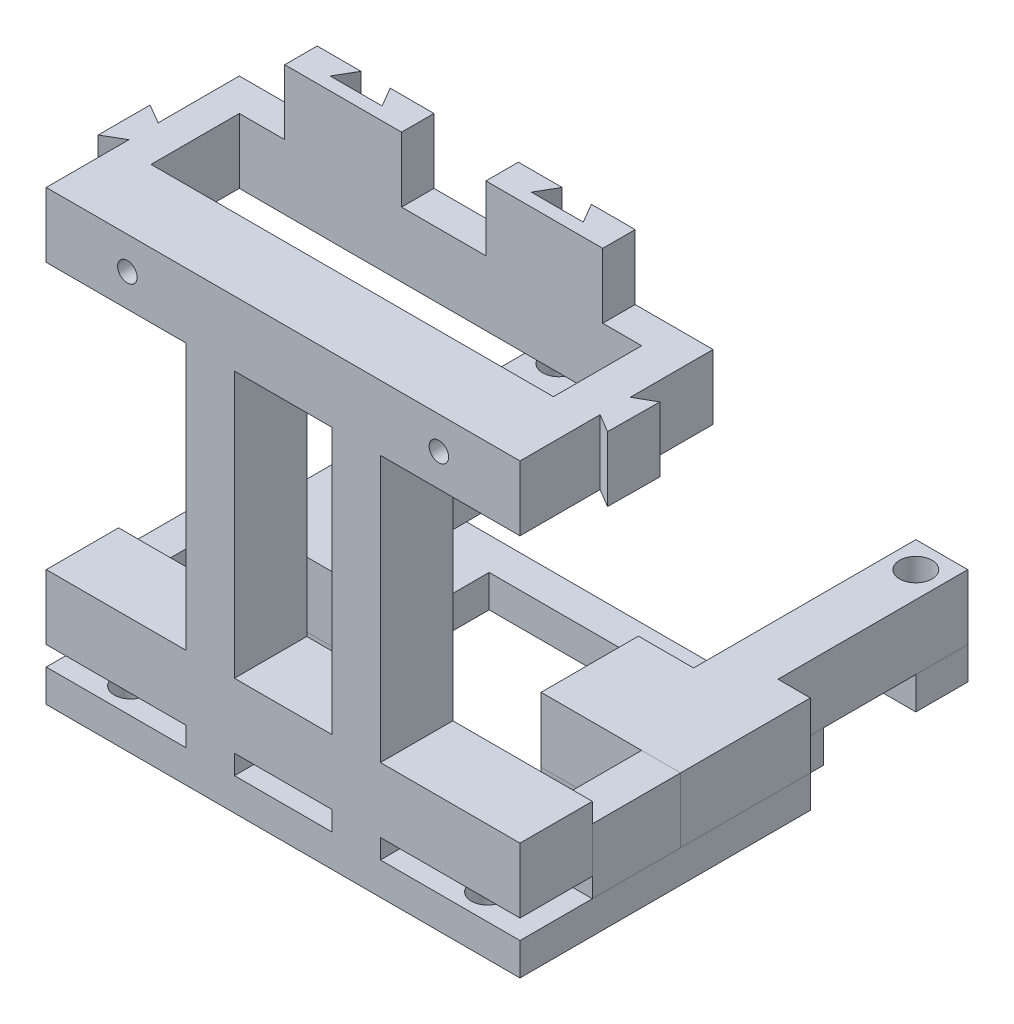
SolidWorks part; units mm, degrees
ref_plane "Front" through (0, 0, 0) normal (0, 0, 1) x (1, 0, 0)
ref_plane "Top" through (0, 0, 0) normal (0, 1, 0) x (1, 0, 0)
ref_plane "Right" through (0, 0, 0) normal (1, 0, 0) x (0, 0, -1)
sketch "Эскиз1" plane through (0, 0, 0) normal (0, 1, 0) x (1, 0, 0)
  line L0 (0, 17.2297) -> (0, -30.0047) construction
  line L1 (-31.5, 1.575) -> (31.5, 1.575)
  line L2 (-31.5, 1.575) -> (-31.5, -1.575)
  line L3 (-31.5, -1.575) -> (31.5, -1.575)
  line L4 (31.5, 1.575) -> (31.5, -1.575)
  line L5 (-31.5, 1.575) -> (31.5, -1.575) construction
  line L6 (-31.5, -1.575) -> (31.5, 1.575) construction
  line L7 (-23.5, -9.575) -> (23.5, -9.575)
  line L8 (-31.5, -1.575) -> (-23.5, -1.575)
  line L9 (-31.5, -1.575) -> (-31.5, -9.575)
  line L10 (-31.5, -9.575) -> (-23.5, -9.575)
  line L11 (-23.5, -1.575) -> (-23.5, -9.575)
  line L12 (-31.5, -1.575) -> (-23.5, -9.575) construction
  line L13 (-31.5, -9.575) -> (-23.5, -1.575) construction
  line L14 (23.5, -1.575) -> (31.5, -1.575)
  line L15 (23.5, -1.575) -> (23.5, -9.575)
  line L16 (23.5, -9.575) -> (31.5, -9.575)
  line L17 (31.5, -1.575) -> (31.5, -9.575)
  line L18 (23.5, -1.575) -> (31.5, -9.575) construction
  line L19 (23.5, -9.575) -> (31.5, -1.575) construction
  line L21 (-31.5, -9.575) -> (-36.5, -9.575)
  line L22 (-31.5, -9.575) -> (-31.5, 15.175)
  line L23 (-31.5, 15.175) -> (-36.5, 15.175)
  line L24 (-36.5, -9.575) -> (-36.5, 15.175)
  line L25 (31.5, -9.575) -> (36.5, -9.575)
  line L26 (31.5, -9.575) -> (31.5, 15.175)
  line L27 (31.5, 15.175) -> (36.5, 15.175)
  line L28 (36.5, -9.575) -> (36.5, 15.175)
  line L29 (-36.5, 15.175) -> (-15, 15.175)
  line L30 (-36.5, 15.175) -> (-36.5, 35.175)
  line L31 (-36.5, 35.175) -> (-15, 35.175)
  line L32 (-15, 15.175) -> (-15, 35.175)
  line L33 (36.5, 15.175) -> (15, 15.175)
  line L34 (36.5, 15.175) -> (36.5, 35.175)
  line L35 (36.5, 35.175) -> (15, 35.175)
  line L36 (15, 15.175) -> (15, 35.175)
  line L37 (-31.5, 64.425) -> (-23.5, 64.425)
  line L38 (-31.5, 64.425) -> (-31.5, 56.425)
  line L39 (-31.5, 56.425) -> (-23.5, 56.425)
  line L40 (-23.5, 64.425) -> (-23.5, 56.425)
  line L41 (-31.5, 64.425) -> (-23.5, 56.425) construction
  line L42 (-31.5, 56.425) -> (-23.5, 64.425) construction
  line L43 (23.5, 64.425) -> (31.5, 64.425)
  line L44 (23.5, 64.425) -> (23.5, 56.425)
  line L45 (23.5, 56.425) -> (31.5, 56.425)
  line L46 (31.5, 64.425) -> (31.5, 56.425)
  line L47 (23.5, 64.425) -> (31.5, 56.425) construction
  line L48 (23.5, 56.425) -> (31.5, 64.425) construction
  line L49 (-15, 35.175) -> (-31.5, 35.175)
  line L50 (-15, 35.175) -> (-15, 42.175)
  line L51 (-15, 42.175) -> (-31.5, 42.175)
  line L52 (-31.5, 35.175) -> (-31.5, 42.175)
  line L53 (15, 35.175) -> (31.5, 35.175)
  line L54 (15, 35.175) -> (15, 42.175)
  line L55 (15, 42.175) -> (31.5, 42.175)
  line L56 (31.5, 35.175) -> (31.5, 42.175)
  line L57 (-15, 42.175) -> (15, 42.175)
  line L58 (-15, 42.175) -> (-15, 37.175)
  line L59 (-15, 37.175) -> (15, 37.175)
  line L60 (15, 42.175) -> (15, 37.175)
  circle A0 centre (-27.5, -5.575) radius 2.5
  circle A1 centre (27.5, -5.575) radius 2.5
  circle A2 centre (-27.5, 60.425) radius 2.5
  circle A3 centre (27.5, 60.425) radius 2.5
  point P0 (0, 0)
  dimension "D1" = 5
  dimension "D2" = 55
  dimension "D10" = 5
  dimension "D12" = 25.25
  dimension "D3" = 8
  dimension "D4" = 3.15
  dimension "D5" = 8
  dimension "D6" = 5
  dimension "D7" = 16.75
  dimension "D8" = 21.5
  dimension "D9" = 20
  dimension "D11" = 8
  dimension "D13" = 7
  dimension "D14" = 5
extrude "Бобышка-Вытянуть1" add sketch "Эскиз1" along normal blind 5 contours L4 L1 L2 L3 | L11 L3 L9 L10 A0 | L17 L3 L15 L16 A1 | L15 L3 L11 L7 | L24 L21 L9 L2 L22 L23 | L29 L32 L31 L30 L23 | L36 L33 L27 L34 L35 | L25 L28 L27 L26 L4 L17 | L40 L37 L38 L39 A2 | L46 L43 L44 L45 A3 | L52 L31 L50 L51 | L35 L56 L55 L54 | L50 L59 L54 L57 region at (0, 0, 0) region at (-34, 0, -2.8) region at (34, 0, -2.8) region at (-27.5, 0, 1.6881) region at (-25.75, 0, -25.175) region at (31.3869, 0, 5.575) region at (25.75, 0, -25.175) region at (0, 0, 5.575) region at (-23.25, 0, -38.675) region at (23.25, 0, -38.675) region at (0, 0, -39.675) region at (-27.5, 0, -64.3119) region at (27.5, 0, -64.3119)
sketch "Эскиз2" plane through (0, 5, 0) normal (0, 1, 0) x (1, 0, 0)
  line L0 (-31.5, 1.575) -> (31.5, 1.575) construction
  line L1 (-15, 1.575) -> (-7.5, 1.575)
  line L2 (-15, 1.575) -> (-15, -9.575)
  line L3 (-15, -9.575) -> (-7.5, -9.575)
  line L4 (-7.5, 1.575) -> (-7.5, -9.575)
  line L5 (-36.5, -9.575) -> (36.5, -9.575) construction
  line L6 (0, 1.575) -> (0, -9.575) construction
  line L7 (7.5, 1.575) -> (15, 1.575)
  line L8 (7.5, 1.575) -> (7.5, -9.575)
  line L9 (7.5, -9.575) -> (15, -9.575)
  line L10 (15, 1.575) -> (15, -9.575)
  dimension "D1" = 7.5
  dimension "D2" = 7.5
extrude "Бобышка-Вытянуть2" add sketch "Эскиз2" along normal blind 64
sketch "Эскиз3" plane through (0, 0, 9.575) normal (0, 0, 1) x (1, 0, 0)
  line L0 (7.5, 69) -> (15, 69) construction
  line L1 (36.5, 69) -> (-36.5, 69)
  line L2 (36.5, 69) -> (36.5, 59)
  line L3 (36.5, 59) -> (-36.5, 59)
  line L4 (-36.5, 69) -> (-36.5, 59)
  line L6 (0, 0) -> (0, 5) construction
  line L7 (-36.5, 0) -> (36.5, 0) construction
  line L8 (-7.5, 5) -> (7.5, 5) construction
  line L9 (-36.5, 5) -> (-36.5, 0) construction
  line L11 (-36.5, 18) -> (36.5, 18)
  line L12 (-36.5, 18) -> (-36.5, 8)
  line L13 (-36.5, 8) -> (36.5, 8)
  line L14 (36.5, 18) -> (36.5, 8)
  circle A0 centre (-24, 64) radius 1.5
  circle A1 centre (24, 64) radius 1.5
  dimension "D2" = 48
  dimension "D4" = 3
  dimension "D1" = 10
  dimension "D3" = 5
extrude "Бобышка-Вытянуть3" add sketch "Эскиз3" against normal up to surface (11.15 mm away) up to face at (-2, 30.8333, -1.575)
sketch "Эскиз4" plane through (0, 5, 0) normal (0, 1, 0) x (1, 0, 0)
  line L0 (-31.5, 15.175) -> (-15, 15.175) construction
  line L1 (-31.5, 64.425) -> (-23.5, 64.425)
  line L2 (-31.5, 64.425) -> (-31.5, 15.175)
  line L3 (-31.5, 15.175) -> (-23.5, 15.175)
  line L4 (-23.5, 64.425) -> (-23.5, 15.175)
  line L5 (-36.5, -9.575) -> (-36.5, 35.175) construction
  line L6 (-31.5, 15.175) -> (-36.5, 15.175)
  line L7 (-31.5, 15.175) -> (-31.5, 23.175)
  line L8 (-31.5, 23.175) -> (-36.5, 23.175)
  line L9 (-36.5, 15.175) -> (-36.5, 23.175)
  line L10 (-15, 15.175) -> (-15, 37.175) construction
  line L11 (-23.5, 15.175) -> (-15, 15.175)
  line L12 (-23.5, 15.175) -> (-23.5, 30.175)
  line L13 (-23.5, 30.175) -> (-15, 30.175)
  line L14 (-15, 15.175) -> (-15, 30.175)
  line L15 (0, 42.175) -> (0, 37.175) construction
  line L16 (31.5, 42.175) -> (-31.5, 42.175) construction
  line L17 (-15, 37.175) -> (15, 37.175) construction
  line L18 (36.5, -9.575) -> (36.5, 35.175) construction
  line L19 (36.5, 15.175) -> (36.5, 35.175)
  line L20 (23.5, 64.425) -> (23.5, 15.175)
  line L21 (23.5, 15.175) -> (36.5, 15.175)
  line L22 (36.5, 35.175) -> (31.5, 35.175)
  line L23 (31.5, 15.175) -> (15, 15.175) construction
  line L24 (15, 15.175) -> (15, 37.175) construction
  line L25 (23.5, 15.175) -> (15, 15.175)
  line L26 (23.5, 15.175) -> (23.5, 30.175)
  line L27 (23.5, 30.175) -> (15, 30.175)
  line L28 (15, 15.175) -> (15, 30.175)
  line L29 (31.5, 35.175) -> (31.5, 64.425)
  line L30 (31.5, 64.425) -> (23.5, 64.425)
  circle A0 centre (-27.5, 60.425) radius 2.5
  circle A1 centre (-27.5, 60.425) radius 2.5 construction
  circle A2 centre (27.5, 60.425) radius 2.5
  circle A3 centre (27.5, 60.425) radius 2.5 construction
  line M8 (36.5, -9.575) -> (36.5, 35.175)
  line M9 (36.5, 35.175) -> (31.5, 35.175)
  line M10 (31.5, 35.175) -> (31.5, 42.175)
  line M11 (31.5, 42.175) -> (-31.5, 42.175)
  line M12 (-31.5, 42.175) -> (-31.5, 35.175)
  line M14 (-36.5, 35.175) -> (-36.5, -9.575)
  line M19 (-31.5, 15.175) -> (-15, 15.175)
  line M20 (-15, 15.175) -> (-15, 37.175)
  line M22 (15, 37.175) -> (15, 15.175)
  line M23 (15, 15.175) -> (31.5, 15.175)
  dimension "D1" = 8
  dimension "D2" = 15
  dimension "D3" = 15
extrude "Бобышка-Вытянуть4" add sketch "Эскиз4" along normal blind 10 separate body contours L4 L2 M11 M12 M19 | L4 L1 L2 A0 M11 | L13 L4 M19 M20 | L21 L20 M23 M8 M9 M10 M11 | L20 L27 M22 M23 | L29 L30 L20 A2 M11 | L2 L8 L6 M14 region at (27.5, 5, -52.4166) region at (29.557, 5, -27.5674) region at (-27.5, 5, -52.4166) region at (-27.5, 5, -28.675) region at (-19.25, 5, -22.675) region at (-34, 5, -19.175) region at (19.25, 5, -22.675)
sketch "Эскиз5" plane through (0, 0, -1.575) normal (0, 0, -1) x (-1, 0, 0)
  line L0 (-30.5, 5) -> (-30.5, 87) construction
  line L1 (-36.5, 5) -> (-30.5, 5)
  line L2 (-36.5, 5) -> (-36.5, 15)
  line L3 (-36.5, 15) -> (-30.5, 15)
  line L4 (-30.5, 5) -> (-30.5, 15)
  line L5 (31.5, 5) -> (31.5, 87) construction
  line L6 (36.5, 5) -> (31.5, 5)
  line L7 (36.5, 5) -> (36.5, 15)
  line L8 (36.5, 15) -> (31.5, 15)
  line L9 (31.5, 5) -> (31.5, 15)
  line L10 (-36.5, 8) -> (-36.5, 18) construction
  line L11 (36.5, 18) -> (36.5, 8) construction
extrude "Бобышка-Вытянуть7" add sketch "Эскиз5" along normal up to surface (13.6 mm away) separate body up to face at (25.75, 10, -15.175)
sketch "Эскиз6" plane through (0, 0, -1.575) normal (0, 0, -1) x (-1, 0, 0)
  line L0 (-30.5, 5) -> (-30.5, 87) construction
  line L1 (-36.5, 69) -> (-30.5, 69)
  line L2 (-36.5, 69) -> (-36.5, 59)
  line L3 (-36.5, 59) -> (-30.5, 59)
  line L4 (-30.5, 69) -> (-30.5, 59)
  line L5 (-15, 59) -> (-36.5, 59) construction
  line L6 (31.5, 5) -> (31.5, 87) construction
  line L7 (36.5, 69) -> (31.5, 69)
  line L8 (36.5, 69) -> (36.5, 59)
  line L9 (36.5, 59) -> (31.5, 59)
  line L10 (31.5, 69) -> (31.5, 59)
  line L11 (36.5, 59) -> (15, 59) construction
extrude "Бобышка-Вытянуть8" add sketch "Эскиз6" along normal up to surface (13.6 mm away) separate body up to face at (25.75, 10, -15.175)
sketch "Эскиз7" plane through (0, 0, -15.175) normal (0, 0, -1) x (-1, 0, 0)
  line L1 (-36.5, 69) -> (36.5, 69)
  line L2 (-36.5, 69) -> (-36.5, 59)
  line L3 (-36.5, 59) -> (36.5, 59)
  line L4 (36.5, 69) -> (36.5, 59)
extrude "Бобышка-Вытянуть9" add sketch "Эскиз7" along normal blind 5
sketch "Эскиз9" plane through (0, 69, 0) normal (0, 1, 0) x (1, 0, 0)
  line L0 (0, -9.575) -> (0, 20.175) construction
  line L1 (-36.5, -9.575) -> (36.5, -9.575) construction
  line L2 (-36.5, 20.175) -> (36.5, 20.175) construction
  line L3 (-15.5, 15.175) -> (-15.5, 20.175) construction
  line L4 (-31.5, 15.175) -> (30.5, 15.175) construction
  line L5 (-17.75, 20.175) -> (-19.5, 17.175)
  line L6 (-19.5, 17.175) -> (-11.5, 17.175)
  line L7 (-11.5, 17.175) -> (-13.25, 20.175)
  line L8 (-13.25, 20.175) -> (-17.75, 20.175)
  line L9 (13.25, 20.175) -> (17.75, 20.175)
  line L10 (11.5, 17.175) -> (13.25, 20.175)
  line L11 (19.5, 17.175) -> (11.5, 17.175)
  line L12 (17.75, 20.175) -> (19.5, 17.175)
  dimension "D1" = 3
  dimension "D2" = 4.5
  dimension "D3" = 8
  dimension "D4" = 15.5
extrude "Вырез-Вытянуть1" cut sketch "Эскиз9" against normal up to next (10 mm away)
sketch "Эскиз10" plane through (0, 69, 0) normal (0, 1, 0) x (1, 0, 0)
  line L0 (-17.75, 20.175) -> (-24.5, 20.175)
  line L1 (-36.5, 20.175) -> (-17.75, 20.175) construction
  line L2 (-24.5, 20.175) -> (-24.5, 15.175)
  line L3 (-31.5, 15.175) -> (30.5, 15.175) construction
  line L4 (-24.5, 15.175) -> (-6.5, 15.175)
  line L5 (-6.5, 15.175) -> (-6.5, 20.175)
  line L6 (-13.25, 20.175) -> (13.25, 20.175) construction
  line L7 (-6.5, 20.175) -> (-13.25, 20.175)
  line L8 (-13.25, 20.175) -> (-11.5, 17.175)
  line L9 (-11.5, 17.175) -> (-19.5, 17.175)
  line L10 (-19.5, 17.175) -> (-17.75, 20.175)
  line L11 (13.25, 20.175) -> (6.5, 20.175)
  line L12 (6.5, 20.175) -> (6.5, 15.175)
  line L13 (6.5, 15.175) -> (24.5, 15.175)
  line L14 (24.5, 15.175) -> (24.5, 20.175)
  line L15 (17.75, 20.175) -> (36.5, 20.175) construction
  line L16 (24.5, 20.175) -> (17.75, 20.175)
  line L17 (19.5, 17.175) -> (17.75, 20.175) construction
  line L18 (17.75, 20.175) -> (19.5, 17.175)
  line L19 (19.5, 17.175) -> (11.5, 17.175)
  line L20 (11.5, 17.175) -> (13.25, 20.175)
  dimension "D1" = 5
  dimension "D2" = 5
  dimension "D3" = 5
  dimension "D4" = 5
extrude "Бобышка-Вытянуть10" add sketch "Эскиз10" along normal up to surface (10 mm away)
sketch "Эскиз11" plane through (0, 69, 0) normal (0, 1, 0) x (1, 0, 0)
  line L0 (-36.5, 3.175) -> (-39.5, 1.425)
  line L1 (-36.5, 20.175) -> (-36.5, -9.575) construction
  line L2 (-39.5, 1.425) -> (-39.5, 9.425)
  line L3 (-39.5, 9.425) -> (-36.5, 7.675)
  line L4 (-36.5, 7.675) -> (-36.5, 3.175)
  line L5 (-36.5, -9.575) -> (36.5, -9.575) construction
  line L6 (-0.13, -9.575) -> (0, 20.175) construction
  line L7 (-26.8, -9.575) -> (26.54, -9.575) construction
  line L8 (-6.5, 20.175) -> (6.5, 20.175) construction
  line L9 (36.3894, 7.3565) -> (36.35, 2.8567)
  line L10 (39.4045, 9.0802) -> (36.3894, 7.3565)
  line L11 (39.3346, 1.0805) -> (39.4045, 9.0802)
  line L12 (36.35, 2.8567) -> (39.3346, 1.0805)
  point P6 (-36.5, 5.425)
  dimension "D1" = 8
  dimension "D2" = 4.5
  dimension "D3" = 3
  dimension "D4" = 15
extrude "Бобышка-Вытянуть11" add sketch "Эскиз11" against normal up to surface (10 mm away) up to face at (-0.1, 59, -9.405)
